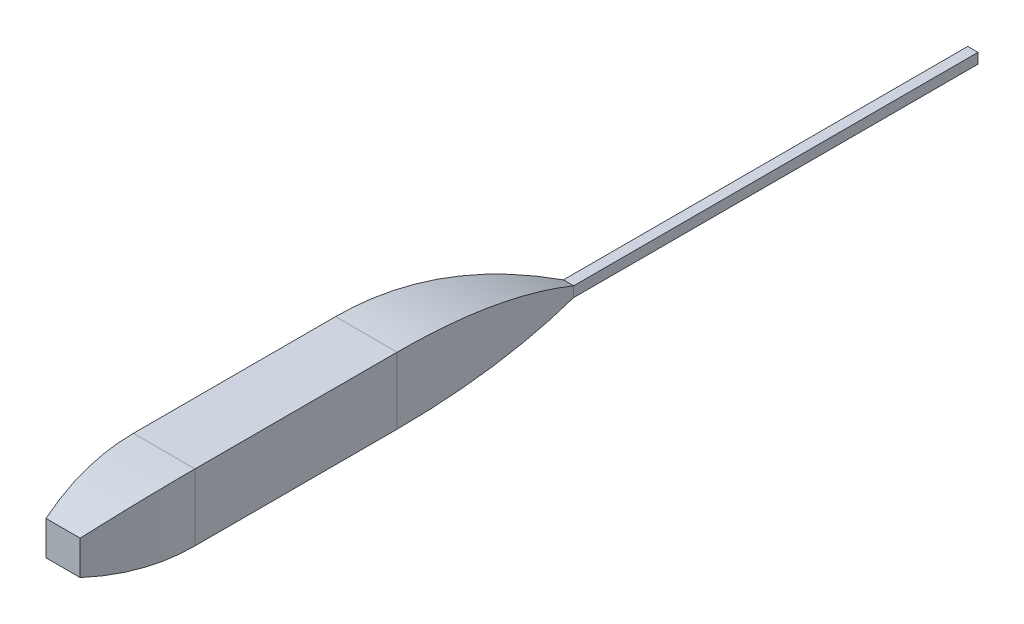
SolidWorks part; units mm, degrees
ref_plane "Front Plane" through (0, 0, 0) normal (0, 0, 1) x (1, 0, 0)
ref_plane "Top Plane"
ref_plane "Right Plane" through (0, 0, 0) normal (1, 0, 0) x (0, 0, -1)
sketch "Sketch2" plane through (0, 0, 0) normal (0, 0, 1) x (1, 0, 0)
  line L0 (0, 0) -> (14.1421, 14.1421) construction
  line L1 (0, -35.75) -> (0, 35.75) construction
  line L2 (33, 0) -> (-33, 0) construction
  line L3 (-16.6421, 16.6421) -> (16.6421, 16.6421)
  line L4 (-14.1421, -14.1421) -> (14.1421, -14.1421)
  line L5 (-14.1421, -14.1421) -> (-14.1421, 14.1421)
  line L6 (-14.1421, 14.1421) -> (14.1421, 14.1421)
  line L7 (14.1421, -14.1421) -> (14.1421, 14.1421)
  line L8 (-14.1421, -14.1421) -> (14.1421, 14.1421) construction
  line L9 (-14.1421, 14.1421) -> (14.1421, -14.1421) construction
  line L10 (16.6421, -16.6421) -> (16.6421, 16.6421)
  line L11 (-16.6421, -16.6421) -> (16.6421, -16.6421)
  line L12 (-16.6421, -16.6421) -> (-16.6421, 16.6421)
  circle A1 centre (10.253, 10.253) radius 1.5
  circle A2 centre (-10.253, 10.253) radius 1.5
  circle A3 centre (-10.253, -10.253) radius 1.5
  circle A4 centre (10.253, -10.253) radius 1.5
  dimension "D2" = 3
  dimension "D1" = 20
  dimension "D3" = 4
  dimension "D4" = 2.5
sketch "Sketch3" plane through (0, 0, 0) normal (1, 0, 0) x (0, 0, -1)
  line L0 (0, 0) -> (98.5, 0) construction
  line L1 (98.5, 32.5) -> (98.5, -32.5) construction
  line L2 (98.5, 0) -> (295.5, 0) construction
  line L3 (0, -16.6421) -> (0, 16.6421) construction
  line L4 (295.5, -32.5) -> (985, -32.5)
  line L5 (49.25, 0) -> (49.25, 32.5)
  line L6 (0, 16.6421) -> (49.25, 32.5) construction
  line L7 (49.25, 32.5) -> (98.5, 32.5) construction
  line L8 (295.5, -32.5) -> (295.5, 32.5) construction
  line L9 (98.5, 32.5) -> (295.5, 32.5)
  line L10 (0, -16.6421) -> (49.25, -32.5) construction
  line L11 (49.25, -32.5) -> (98.5, -32.5) construction
  line L12 (98.5, -32.5) -> (295.5, -32.5)
  line L13 (985, -32.5) -> (985, -22.5)
  line L14 (492.5, -22.5) -> (985, -22.5)
  line L15 (394, -22.5) -> (394, 32.5) construction
  line L16 (295.5, 32.5) -> (394, 32.5) construction
  line L17 (394, 32.5) -> (492.5, -22.5) construction
  line L18 (492.5, -22.5) -> (295.5, -22.5)
  line L19 (0, -16.6421) -> (0, 16.6421)
  spline S0 degree 2 poles (0, 16.6421) (49.25, 32.5) (98.5, 32.5) knots 0 0 0 1 1 1
  spline S1 degree 2 poles (0, -16.6421) (49.25, -32.5) (98.5, -32.5) knots 0 0 0 1 1 1
  spline S2 degree 2 poles (295.5, 32.5) (394, 32.5) (492.5, -22.5) knots 0 0 0 1 1 1
  point P3 (49.25, 0)
  point P6 (98.5, 0)
  point P7 (394, -22.5)
  point P18 (295.5, 0)
  point P26 (492.5, -22.5)
  point P28 (295.5, 32.5)
  point P29 (394, 32.5)
  point P34 (0, 0)
  dimension "D1" = 65
  dimension "D2" = 98.5
  dimension "D3" = 197
  dimension "D4" = 689.5
  dimension "D5" = 10
  dimension "D6" = 197
  dimension "D7" = 98.5
sketch "Sketch4" plane through (0, 0, 0) normal (0, 1, 0) x (1, 0, 0)
  line L0 (0, 0) -> (0, 98.5)
  line L1 (0, 98.5) -> (0, 295.5)
  line L2 (0, 295.5) -> (0, 886.5)
  line L3 (0, 492.5) -> (0, 985) construction
  line L4 (0, 295.5) -> (0, 985) construction
  line L5 (-16.6421, 0) -> (16.6421, 0)
  line L6 (-16.6421, 0) -> (16.6421, 0) construction
  line L7 (-30, 49.25) -> (30, 49.25) construction
  line L8 (-30, 98.5) -> (30, 98.5) construction
  line L9 (-30, 295.5) -> (30, 295.5) construction
  line L10 (-30, 394) -> (30, 394) construction
  line L11 (-5, 886.5) -> (5, 886.5)
  line L12 (30, 98.5) -> (30, 49.25) construction
  line L13 (30, 49.25) -> (16.6421, 0) construction
  line L14 (30, 98.5) -> (30, 295.5)
  line L15 (5, 886.5) -> (5, 295.5) construction
  line L16 (-5, 886.5) -> (-5, 295.5) construction
  line L17 (30, 295.5) -> (30, 394) construction
  line L18 (30, 394) -> (5, 492.5) construction
  line L19 (5, 492.5) -> (5, 886.5)
  line L20 (-30, 295.5) -> (-30, 394) construction
  line L21 (-30, 394) -> (-5, 492.5) construction
  line L22 (-5, 492.5) -> (-5, 886.5)
  line L23 (-30, 98.5) -> (-30, 49.25) construction
  line L24 (-30, 49.25) -> (-16.6421, 0) construction
  line L25 (-30, 98.5) -> (-30, 295.5)
  spline S0 degree 2 poles (30, 98.5) (30, 49.25) (16.6421, 0) knots 0 0 0 1 1 1
  spline S1 degree 2 poles (30, 295.5) (30, 394) (5, 492.5) knots 0 0 0 1 1 1
  spline S2 degree 2 poles (-30, 295.5) (-30, 394) (-5, 492.5) knots 0 0 0 1 1 1
  spline S3 degree 2 poles (-30, 98.5) (-30, 49.25) (-16.6421, 0) knots 0 0 0 1 1 1
  point P4 (5, 492.5)
  point P16 (0, 0)
  point P20 (0, 49.25)
  point P23 (0, 98.5)
  point P25 (0, 295.5)
  point P29 (0, 394)
  point P32 (0, 886.5)
  point P34 (0, 492.5)
  point P44 (0, 0)
  point P45 (0, 98.5)
  dimension "D1" = 60
  dimension "D2" = 60
  dimension "D3" = 60
  dimension "D4" = 10
  dimension "D5" = 197
  dimension "D6" = 591
extrude "Boss-Extrude1" add sketch "Sketch4" along normal blind 50 and the other way blind 50 contours S2 L22 L11 L19 S1 L14 S0 L5 S3 L25
extrude "Cut-Extrude1" cut sketch "Sketch3" against normal blind 50 and the other way blind 50 flip side to cut contours S2 L9 S0 L19 S1 L12 L4 L13 L14
